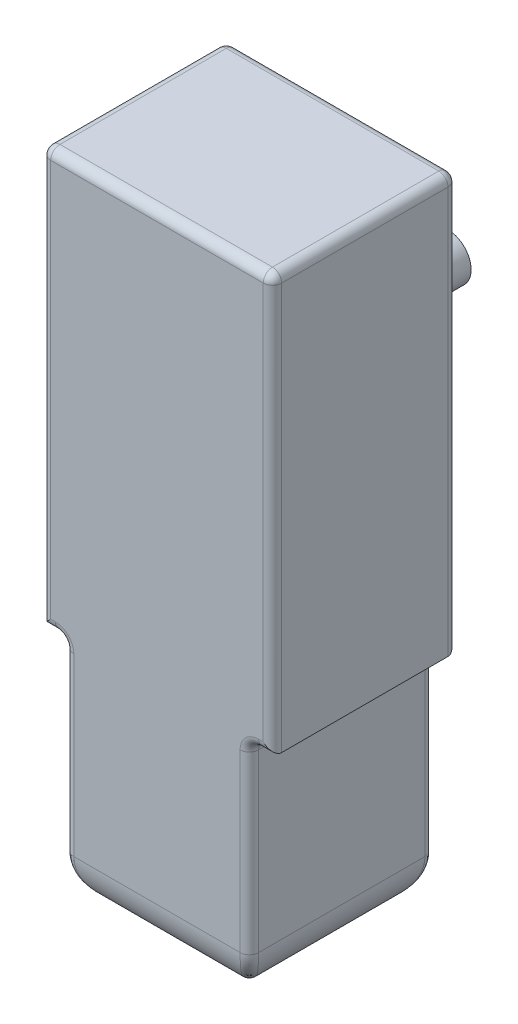
SolidWorks part; units mm, degrees
ref_plane "Front Plane" through (0, 0, 0) normal (0, 0, 1) x (1, 0, 0)
ref_plane "Top Plane" through (0, 0, 0) normal (0, 1, 0) x (1, 0, 0)
ref_plane "Right Plane" through (0, 0, 0) normal (1, 0, 0) x (0, 0, -1)
sketch "Sketch1" plane through (0, 0, 0) normal (0, 0, 1) x (1, 0, 0)
  line L0 (22.5, 25) -> (-2.5, 25)
  line L1 (0, 0) -> (20, 0)
  line L2 (0, 0) -> (0, 25)
  line L3 (0, 25) -> (20, 25)
  line L4 (20, 0) -> (20, 25)
  line L5 (-2.5, 25) -> (-2.5, 70)
  line L6 (-2.5, 70) -> (22.5, 70)
  line L7 (22.5, 70) -> (22.5, 25)
  circle A0 centre (10, 50) radius 2.5
  dimension "D8" = 5
  dimension "D1" = 20
  dimension "D2" = 25
  dimension "D3" = 25
  dimension "D4" = 45
  dimension "D5" = 2.5
  dimension "D6" = 2.5
extrude "Boss-Extrude1" add sketch "Sketch1" along normal blind 20 contours L7 L6 L5 L0 A0 | L1 L4 L0 L2 region at (10, 47.4556, 0) region at (10, 12.5, 0)
sketch "Sketch2" plane through (0, 0, 20) normal (0, 0, 1) x (1, 0, 0)
  circle A0 centre (10, 50) radius 2.5
extrude "Boss-Extrude2" add sketch "Sketch2" against normal blind 31.5
fillet "Fillet1" radius 1 18 edges at (21.25, 25, 0) (21.25, 25, 20) (-1.25, 25, 20) (-1.25, 25, 0) (10, 70, 20) (22.5, 70, 10) (-2.5, 70, 10) (10, 70, 0) (-2.5, 47.5, 0) (0, 12.5, 0) (-2.5, 47.5, 20) (0, 12.5, 20) (20, 12.5, 20) (22.5, 47.5, 20) (22.5, 47.5, 0) (20, 12.5, 0) (0, 25, 10) (20, 25, 10)
fillet "Fillet2" radius 5 8 edges at (0.2929, 0, 19.7071) (10, 0, 20) (19.7071, 0, 19.7071) (20, 0, 10) (19.7071, 0, 0.2929) (10, 0, 0) (0.2929, 0, 0.2929) (0, 0, 10)
